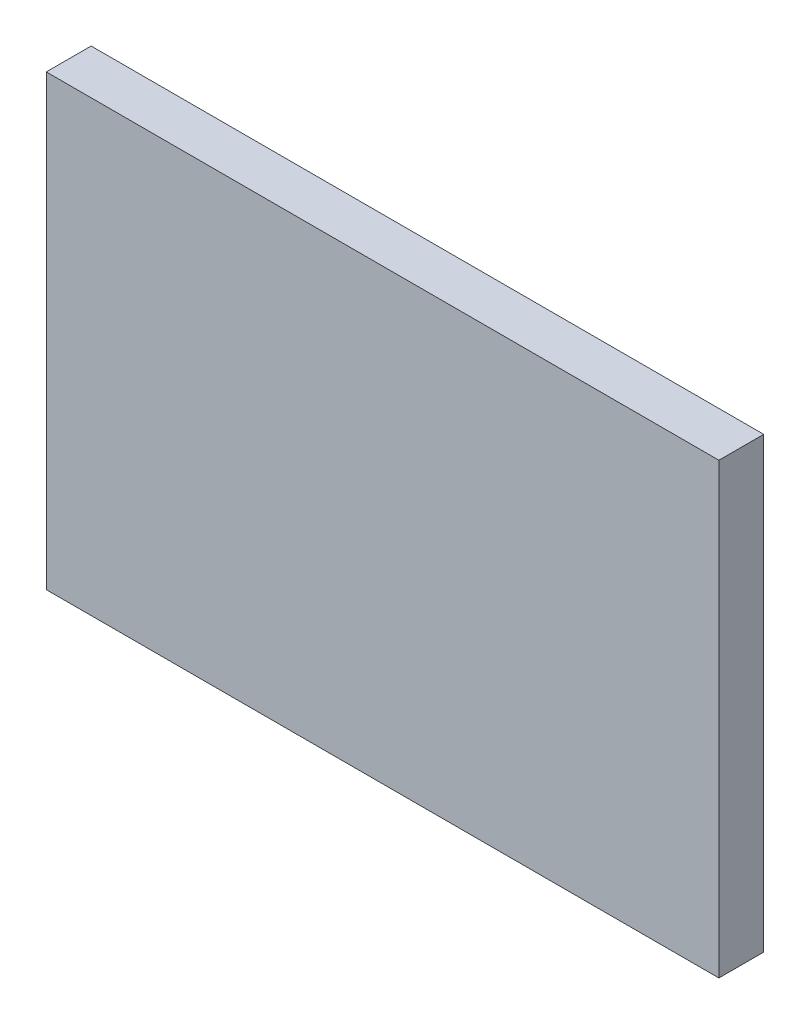
SolidWorks part; units mm, degrees
material "Лист 4,0 ГОСТ 19903-2015 / Ст3сп ГОСТ 14637-89"
ref_plane "Спереди" through (0, 0, 0) normal (0, 0, 1) x (1, 0, 0)
ref_plane "Сверху" through (0, 0, 0) normal (0, 1, 0) x (1, 0, 0)
ref_plane "Справа" through (0, 0, 0) normal (1, 0, 0) x (0, 0, -1)
sketch "Эскиз1" plane through (0, 0, 0) normal (0, 0, 1) x (1, 0, 0)
  line L1 (-30, -20) -> (30, -20)
  line L2 (-30, -20) -> (-30, 20)
  line L3 (-30, 20) -> (30, 20)
  line L4 (30, -20) -> (30, 20)
extrude "Бобышка-Вытянуть1" add sketch "Эскиз1" along normal blind 4
